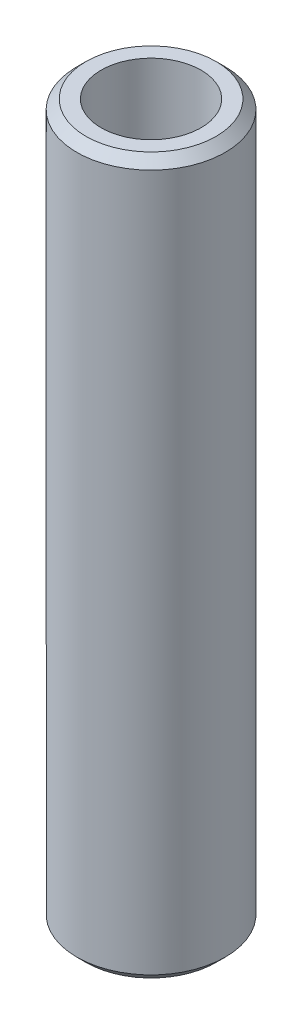
SolidWorks part; units mm, degrees
ref_plane "Front Plane" through (0, 0, 0) normal (0, 0, 1) x (1, 0, 0)
ref_plane "Top Plane" through (0, 0, 0) normal (0, 1, 0) x (1, 0, 0)
ref_plane "Right Plane" through (0, 0, 0) normal (1, 0, 0) x (0, 0, -1)
sketch "Sketch1" plane through (0, 0, 0) normal (0, 1, 0) x (1, 0, 0)
  circle A0 centre (0, 0) radius 17.5
  dimension "SHAFT_OD" = 35
extrude "Boss-Extrude1" add sketch "Sketch1" along normal blind 168.7305
sketch "Sketch2" plane through (0, 0, 0) normal (0, 1, 0) x (1, 0, 0)
  circle A0 centre (0, 0) radius 11.7881
  dimension "BORE_D" = 23.5762
extrude "Cut-Extrude1" cut sketch "Sketch2" along normal through all
chamfer "Chamfer1" distance 2.1768 angle 45 2 edges at (0, 168.7305, 17.5) (0, 0, 17.5)
